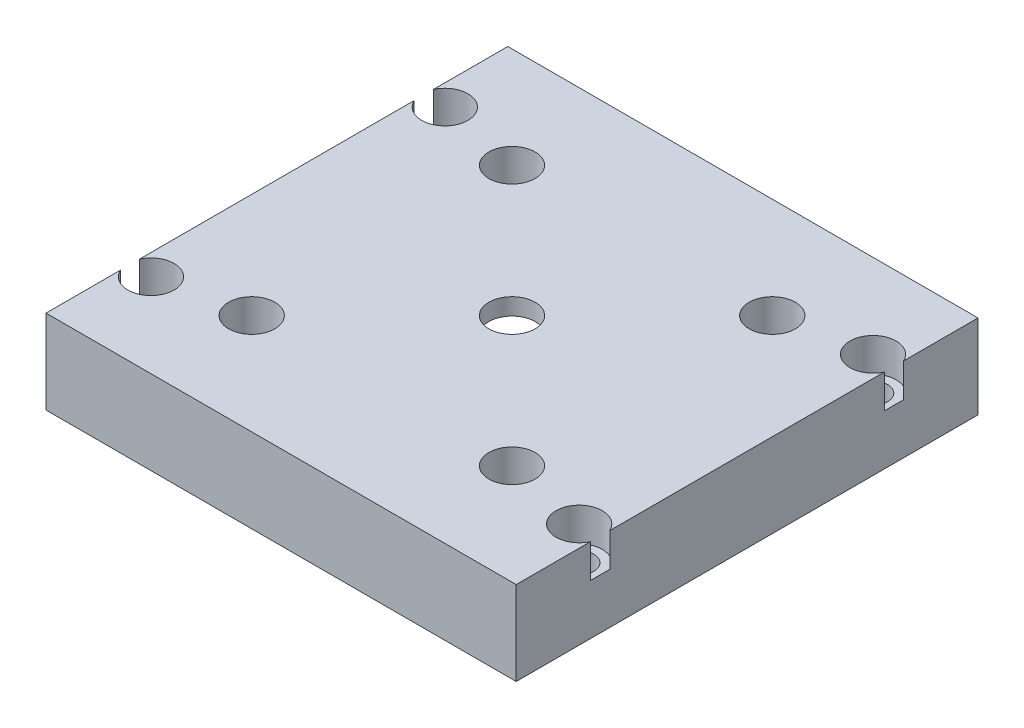
SolidWorks part; units mm, degrees
ref_plane "Front Plane" through (0, 0, 0) normal (0, 0, 1) x (1, 0, 0)
ref_plane "Top Plane" through (0, 0, 0) normal (0, 1, 0) x (1, 0, 0)
ref_plane "Right Plane" through (0, 0, 0) normal (1, 0, 0) x (0, 0, -1)
sketch "Sketch2" plane through (0, 0, 0) normal (0, 1, 0) x (1, 0, 0)
  line L1 (-28, 27.5) -> (28, 27.5)
  line L2 (-28, 27.5) -> (-28, -27.5)
  line L3 (-28, -27.5) -> (28, -27.5)
  line L4 (28, 27.5) -> (28, -27.5)
  line L5 (-28, 27.5) -> (28, -27.5) construction
  line L6 (-28, -27.5) -> (28, 27.5) construction
  point P0 (0, 0)
extrude "Boss-Extrude1" add sketch "Sketch2" along normal blind 5
sketch "Sketch4" plane through (0, 0, 0) normal (0, -1, 0) x (1, 0, 0)
  circle A0 centre (0, 0) radius 11.5
extrude "Cut-Extrude1" cut sketch "Sketch4" against normal blind 3
sketch "Sketch5" plane through (0, 5, 0) normal (0, 1, 0) x (1, 0, 0)
  line L1 (28, 27.5) -> (-28, 27.5) construction
  line L2 (-28, 27.5) -> (-28, -27.5) construction
  line L3 (-28, -27.5) -> (28, -27.5) construction
  line L4 (28, -27.5) -> (28, 27.5) construction
  circle A0 centre (-25.5, 17.5) radius 1.75
  circle A1 centre (25.5, -17.5) radius 1.75
  circle A2 centre (-25.5, -17.5) radius 1.75
  circle A3 centre (25.5, 17.5) radius 1.75
  dimension "D1" = 10
  dimension "D3" = 10
  dimension "D2" = 2.5
  dimension "D4" = 2.5
extrude "Cut-Extrude3" cut sketch "Sketch5" against normal blind 54
sketch "Sketch6" plane through (0, 0, 0) normal (0, -1, 0) x (1, 0, 0)
  line L0 (-23, 22.5) -> (-23, -22.5)
  line L1 (-28, 27.5) -> (28, 27.5) construction
  line L2 (28, -27.5) -> (-28, -27.5) construction
  line L3 (-23, -22.5) -> (23, -22.5)
  line L4 (28, 27.5) -> (28, -27.5) construction
  line L5 (23, -22.5) -> (23, 22.5)
  line L6 (23, 22.5) -> (-23, 22.5)
  line L8 (-28, 27.5) -> (28, 27.5)
  line L9 (-28, 27.5) -> (-28, -27.5)
  line L10 (-28, -27.5) -> (28, -27.5)
  line L11 (28, 27.5) -> (28, -27.5)
  line L12 (-28, 27.5) -> (28, -27.5) construction
  line L13 (-28, -27.5) -> (28, 27.5) construction
  circle A0 centre (-25.5, 17.5) radius 1.75 construction
  point P11 (0, 0)
  dimension "D1" = 2.5
  dimension "D2" = 5
  dimension "D3" = 5
  dimension "D4" = 5
extrude "Boss-Extrude2" add sketch "Sketch6" along normal blind 5
sketch "Sketch3" plane through (0, 5, 0) normal (0, 1, 0) x (1, 0, 0)
  circle A0 centre (0, 0) radius 2.75
  circle A5 centre (-15.5, 15.5) radius 1.75
  circle A6 centre (15.5, 15.5) radius 1.75
  circle A7 centre (15.5, -15.5) radius 1.75
  circle A8 centre (-15.5, -15.5) radius 1.75
extrude "Cut-Extrude2" cut sketch "Sketch3" against normal blind 12
extrude "Cut-Extrude4" cut sketch "Sketch5<2>" against normal blind 33
sketch "Sketch5<2>" plane through (0, 5, 0) normal (0, 1, 0) x (1, 0, 0) same geometry as "Sketch5"
sketch "Sketch7" plane through (0, 5, 0) normal (0, 1, 0) x (1, 0, 0)
  circle A0 centre (-15.5, 15.5) radius 2.75
  circle A1 centre (15.5, 15.5) radius 2.75
  circle A2 centre (15.5, -15.5) radius 2.75
  circle A3 centre (-15.5, -15.5) radius 2.75
  circle A4 centre (-25.5, 17.5) radius 2.75
  circle A5 centre (-25.5, -17.5) radius 2.75
  circle A6 centre (25.5, 17.5) radius 2.75
  circle A7 centre (25.5, -17.5) radius 2.75
extrude "Cut-Extrude5" cut sketch "Sketch7" against normal blind 4
sketch "Sketch8" plane through (0, 3, 0) normal (0, -1, 0) x (1, 0, 0)
  circle A0 centre (0, 0) radius 2.75
sketch "Sketch9" plane through (0, 10.75, 0) normal (0, 1, 0) x (1, 0, 0)
  circle A0 centre (0, 0) radius 2.5
